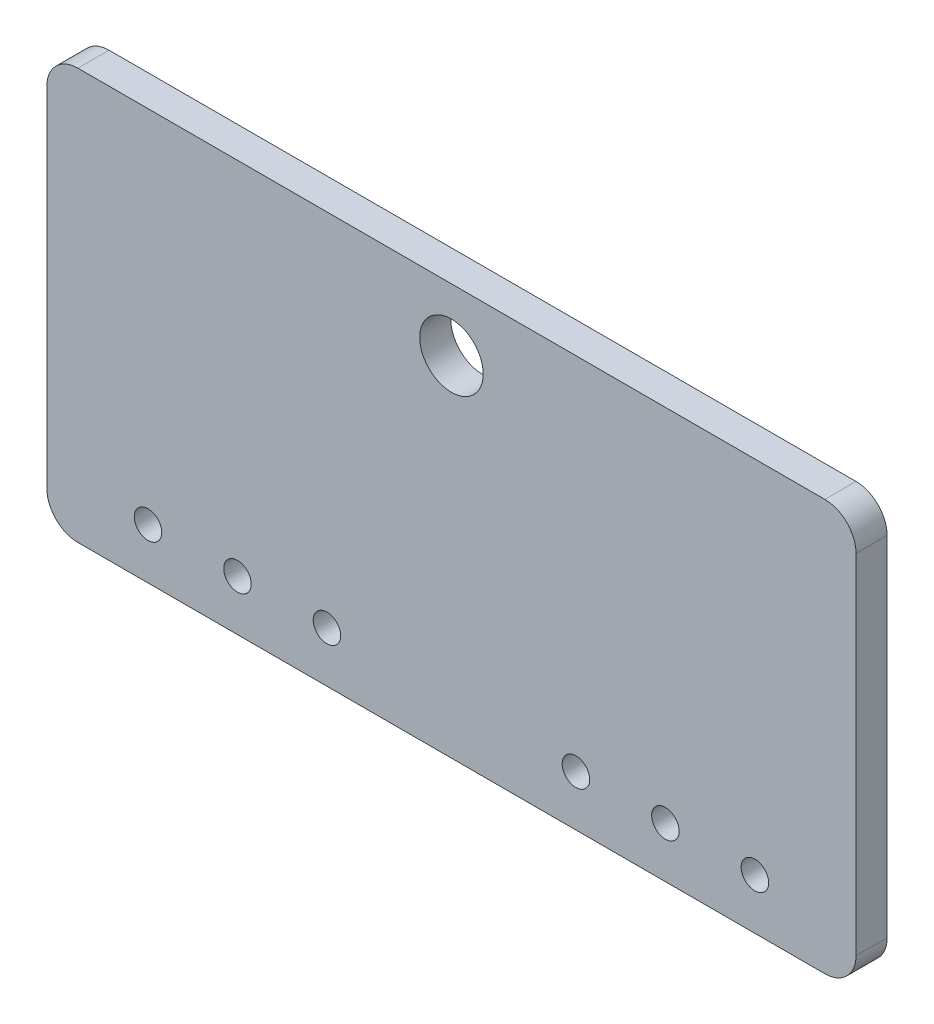
SolidWorks part; units mm, degrees
material "Acrylic (Medium-high impact)"
ref_plane "Front Plane" through (0, 0, 0) normal (0, 0, 1) x (1, 0, 0)
ref_plane "Top Plane" through (0, 0, 0) normal (0, 1, 0) x (1, 0, 0)
ref_plane "Right Plane" through (0, 0, 0) normal (1, 0, 0) x (0, 0, -1)
sketch "Sketch1" plane through (0, 0, 0) normal (0, 0, 1) x (1, 0, 0)
  line L1 (165.1, 83.82) -> (0, 83.82)
  line L2 (165.1, 83.82) -> (165.1, 0)
  line L3 (165.1, 0) -> (0, 0)
  line L4 (0, 83.82) -> (0, 0)
  line L5 (165.1, 83.82) -> (0, 0) construction
  line L6 (165.1, 0) -> (0, 83.82) construction
  point P0 (82.55, 41.91)
  dimension "D1" = 83.82
  dimension "D2" = 165.1
extrude "Boss-Extrude1" add sketch "Sketch1" along normal blind 6.35
hole_wizard "#10 Clearance Hole1" positions "Sketch6" profile "Sketch7" hole size "#10" standard "ANSI Inch" end condition through all
sketch "Sketch6" plane through (0, 0, 6.35) normal (0, 0, 1) x (1, 0, 0)
  line L2 (0, 0) -> (165.1, 0) construction
  line L3 (57.15, 10.3124) -> (107.95, 10.3124) construction
  line L5 (82.55, 0) -> (82.55, 10.3124) construction
  line L6 (20.6375, 10.3124) -> (57.15, 10.3124) construction
  line L9 (107.95, 10.3124) -> (144.4625, 10.3124) construction
  point P0 (20.6375, 10.3124)
  point P11 (57.15, 10.3124)
  point P13 (107.95, 10.3124)
  point P15 (144.4625, 10.3124)
  point P29 (38.8938, 10.3124)
  point P31 (126.2063, 10.3124)
  point P44 (0, 0)
  point P45 (38.8938, 10.3124)
  point P46 (0, 0)
  point P47 (126.2063, 10.3124)
  dimension "D1" = 36.5125
  dimension "D2" = 10.3124
  dimension "D5" = 50.8
sketch "Sketch7" plane through (20.6375, 10.3124, 6.35) normal (1, 0, 0) x (0, -1, 0)
  line L0 (0, 0) -> (0, 6.35)
  line L1 (0, 6.35) -> (2.8067, 6.35)
  line L2 (2.8067, 6.35) -> (2.8067, 0)
  line L5 (2.8067, 0) -> (0, 0)
  line L11 (0, -6.35) -> (0, 107.95) construction
  dimension "Thru Hole Dia." = 5.6134
  dimension "Thru Hole Depth" = 6.35
fillet "Fillet1" radius 6.35 4 edges at (165.1, 0, 3.175) (165.1, 83.82, 3.175) (0, 83.82, 3.175) (0, 0, 3.175)
sketch "Sketch8" plane through (0, 0, 6.35) normal (0, 0, 1) x (1, 0, 0)
  line L0 (6.35, 0) -> (158.75, 0) construction
  line L1 (158.75, 83.82) -> (6.35, 83.82) construction
  circle A0 centre (82.55, 71.12) radius 6.477
  point P6 (82.55, 0)
  dimension "D1" = 12.954
  dimension "D2" = 12.7
extrude "Cut-Extrude1" cut sketch "Sketch8" against normal through all
